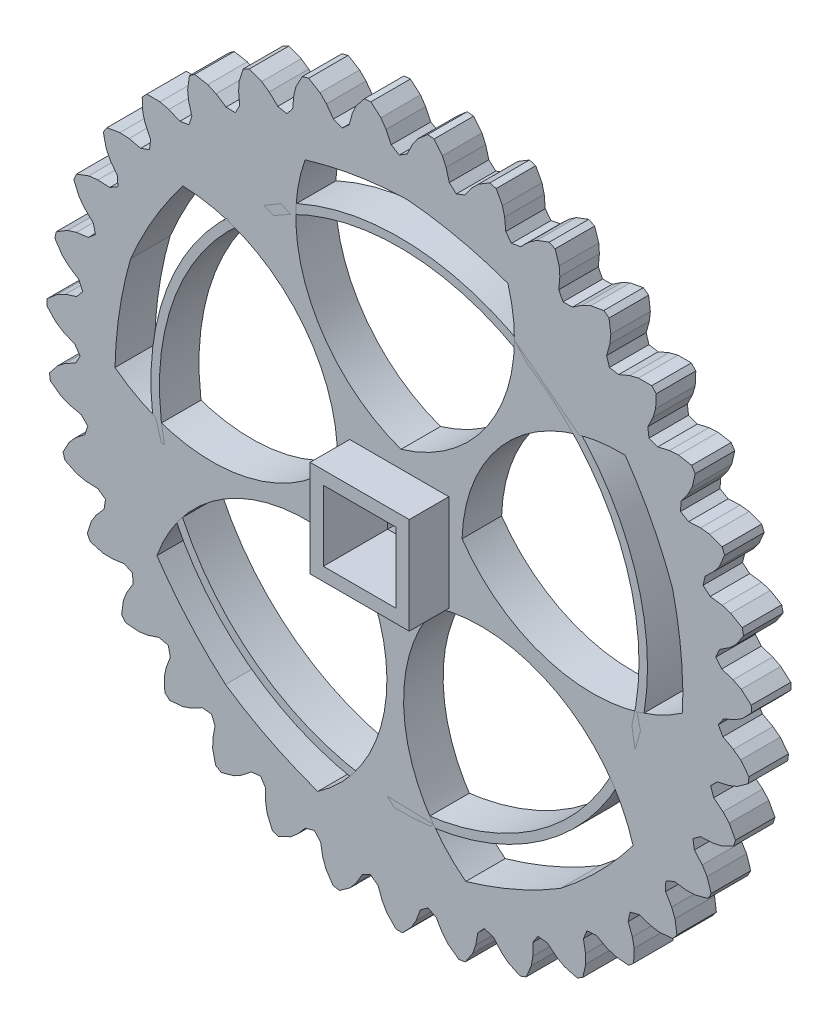
SolidWorks part; units mm, degrees
ref_plane "Front Plane" through (0, 0, 0) normal (0, 0, 1) x (1, 0, 0)
ref_plane "Top Plane" through (0, 0, 0) normal (0, 1, 0) x (1, 0, 0)
ref_plane "Right Plane" through (0, 0, 0) normal (1, 0, 0) x (0, 0, -1)
sketch "Sketch1" plane through (0, 0, 0) normal (0, 0, 1) x (1, 0, 0)
  line L1 (3.675, -3.55) -> (-3.675, -3.55)
  line L2 (3.675, -3.55) -> (3.675, 3.55)
  line L3 (3.675, 3.55) -> (-3.675, 3.55)
  line L4 (-3.675, -3.55) -> (-3.675, 3.55)
  circle A0 centre (0, 0) radius 35.65
  point P3 (0, 3.55)
  point P9 (-3.675, 0)
  dimension "D1" = 71.3
  dimension "D2" = 7.35
  dimension "D3" = 7.1
extrude "Boss-Extrude1" add sketch "Sketch1" along normal blind 4
sketch "Sketch2" plane through (0, 0, 0) normal (0, 0, 1) x (1, 0, 0)
  line L0 (0, 0) -> (0, 36.903) construction
  line L1 (0, 32.3049) -> (-0.8069, 32.8033)
  line L2 (-0.8069, 32.8033) -> (-1.33, 33.8931)
  line L3 (-1.33, 33.8931) -> (-1.8557, 34.6487)
  line L4 (-1.8557, 34.6487) -> (-2.8665, 35.5346)
  line L5 (-2.8665, 35.5346) -> (-1.8557, 36.3071)
  line L6 (-1.8557, 36.3071) -> (0, 36.903)
  line L7 (1.8557, 36.3071) -> (0, 36.903)
  line L8 (2.8665, 35.5346) -> (1.8557, 36.3071)
  line L9 (1.8557, 34.6487) -> (2.8665, 35.5346)
  line L10 (1.33, 33.8931) -> (1.8557, 34.6487)
  line L11 (0.8069, 32.8033) -> (1.33, 33.8931)
  line L12 (0, 32.3049) -> (0.8069, 32.8033)
  circle A22 centre (0, 0) radius 35.65 construction
  dimension "D5" = 0.5258
  dimension "D6" = 0.7556
  dimension "D9" = 0.5959
  dimension "D1" = 0.8069
  dimension "D2" = 0.4984
  dimension "D3" = 0.5231
  dimension "D4" = 1.0898
  dimension "D7" = 0.8858
  dimension "D8" = 1.8557
  dimension "D10" = 1.0107
  dimension "D11" = 0.7725
  dimension "D12" = 1.0107
extrude "Cut-Extrude1" cut sketch "Sketch2" along normal through all
pattern_circular "CirPattern1" count 35 over 360 about axis through (0, 0, 4) along (0, 0, -1) of "Cut-Extrude1"
sketch "Sketch3" plane through (0, 0, 0) normal (0, 0, 1) x (1, 0, 0)
  circle A0 centre (0, 0) radius 29.75
  dimension "D1" = 59.5
sketch "Sketch4" plane through (0, 0, 0) normal (0, 0, 1) x (1, 0, 0)
  line L0 (0, 0) -> (0.7854, 28.8152) construction
  arc A1 (0.7854, 28.8152) -> (-9.5267, 27.1273) centre (2.0438, -11.2177) ccw
  arc A2 (0.7854, 28.8152) -> (10.9903, 26.5681) centre (-2.6519, -11.0897) cw
  arc A4 (0.1805, 6.623) -> (-9.5267, 27.1273) centre (5.5791, 21.7288) cw
  arc A5 (0.1805, 6.623) -> (10.9903, 26.5681) centre (-4.3872, 22.0004) ccw
extrude "Cut-Extrude2" cut sketch "Sketch4" along normal through all both
sketch "Sketch5" plane through (0, 0, 0) normal (0, 0, 1) x (1, 0, 0)
  circle A0 centre (0, 0) radius 25.1098
  circle A1 centre (0, 0) radius 24.2496
extrude "Boss-Extrude2" add sketch "Sketch5" along normal through all separate body
pattern_circular "CirPattern2" count 5 over 360 about axis through (0, 0, 4) along (0, 0, -1) of "Cut-Extrude2" reverse direction yes
chamfer "Chamfer1" distance 1.5 distance2 0.5 4 edges at (-3.675, 0, 0) (0, -3.55, 0) (3.675, 0, 0) (0, 3.55, 0) first distance on face at (-3.675, 0, 2) first distance on face at (0, -3.55, 2) first distance on face at (3.675, 0, 2) first distance on face at (0, 3.55, 2)
sketch "Sketch6" plane through (0, 0, 4) normal (0, 0, 1) x (1, 0, 0)
  line L1 (-3.675, 3.55) -> (3.675, 3.55)
  line L2 (-3.675, 3.55) -> (-3.675, -3.55)
  line L3 (-3.675, -3.55) -> (3.675, -3.55)
  line L4 (3.675, 3.55) -> (3.675, -3.55)
  line L5 (-5.0131, 4.8881) -> (5.0131, 4.8881)
  line L6 (-5.0131, 4.8881) -> (-5.0131, -4.8881)
  line L7 (-5.0131, -4.8881) -> (5.0131, -4.8881)
  line L8 (5.0131, 4.8881) -> (5.0131, -4.8881)
  dimension "D1" = 1.3381
  dimension "D2" = 1.3381
  dimension "D3" = 1.3381
  dimension "D4" = 1.3381
extrude "Boss-Extrude3" add sketch "Sketch6" along normal blind 4
equation "\"padding\"=1.33807"
equation "\"D1@Sketch6\"=\"padding\""
equation "\"D2@Sketch6\"=\"padding\""
equation "\"D3@Sketch6\"=\"padding\""
equation "\"D4@Sketch6\"=\"padding\""
